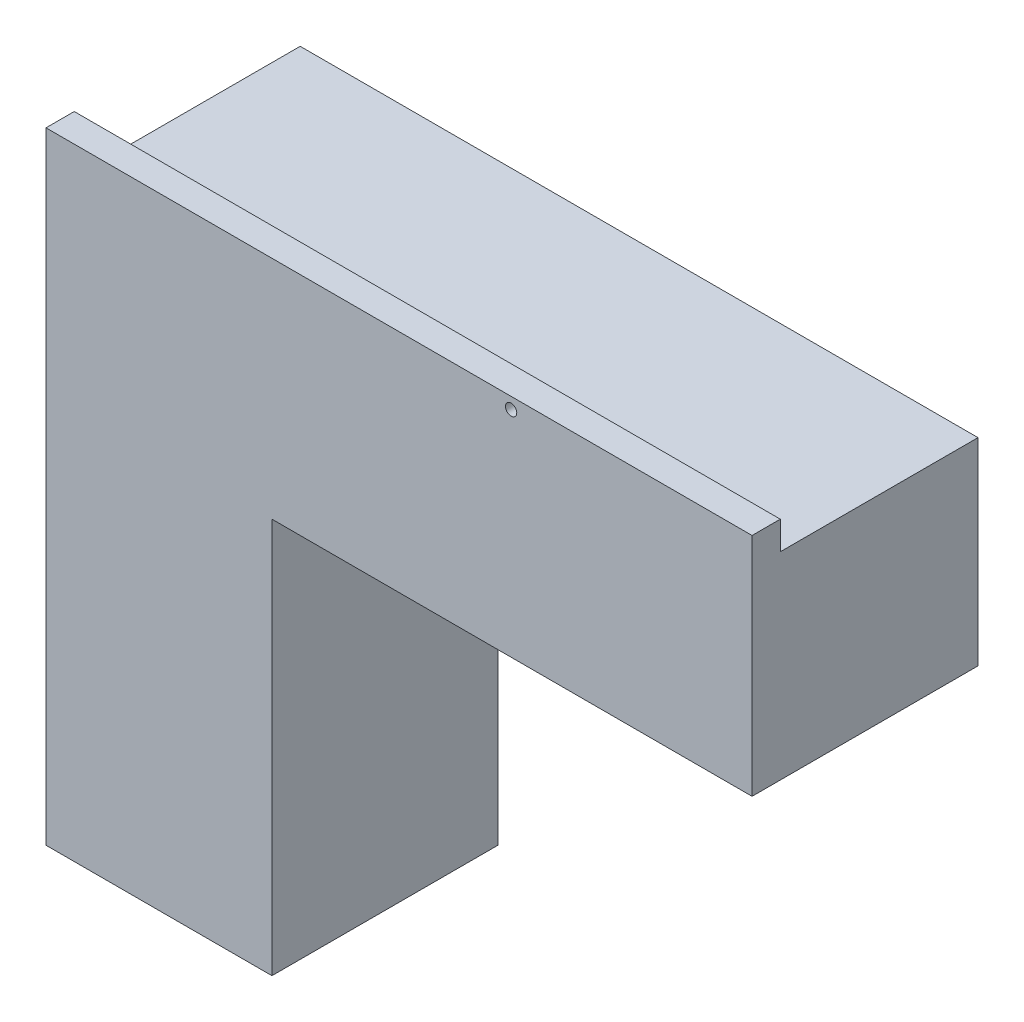
SolidWorks part; units mm, degrees
ref_plane "Спереди" through (0, 0, 0) normal (0, 0, 1) x (1, 0, 0)
ref_plane "Сверху" through (0, 0, 0) normal (0, 1, 0) x (1, 0, 0)
ref_plane "Справа" through (0, 0, 0) normal (1, 0, 0) x (0, 0, -1)
sketch "Эскиз1" plane through (0, 0, 0) normal (0, 0, 1) x (1, 0, 0)
  line L0 (0, 0) -> (0, 220)
  line L1 (0, 220) -> (250, 220)
  line L2 (250, 220) -> (250, 140)
  line L3 (250, 140) -> (80, 140)
  line L4 (80, 140) -> (80, 0)
  line L5 (80, 0) -> (0, 0)
extrude "Бобышка-Вытянуть1" add sketch "Эскиз1" along normal blind 80
sketch "Эскиз2" plane through (0, 0, 0) normal (0, -1, 0) x (1, 0, 0)
  line L1 (0, 0) -> (10, 0)
  line L2 (0, 0) -> (0, 70)
  line L3 (0, 70) -> (10, 70)
  line L4 (10, 0) -> (10, 70)
extrude "Вырез-Вытянуть1" cut sketch "Эскиз2" against normal blind 250
sketch "Эскиз3" plane through (250, 0, 0) normal (1, 0, 0) x (0, 0, -1)
  line L1 (0, 220) -> (-70, 220)
  line L2 (0, 220) -> (0, 210)
  line L3 (0, 210) -> (-70, 210)
  line L4 (-70, 220) -> (-70, 210)
extrude "Вырез-Вытянуть2" cut sketch "Эскиз3" against normal blind 250
sketch "Эскиз4" plane through (0, 0, 80) normal (0, 0, 1) x (1, 0, 0)
  circle A0 centre (164.6882, 215.9215) radius 2
  point P2 (151.3229, 215.9215)
  point P3 (164.6882, 215.9215)
extrude "Вырез-Вытянуть3" cut sketch "Эскиз4" against normal blind 10
